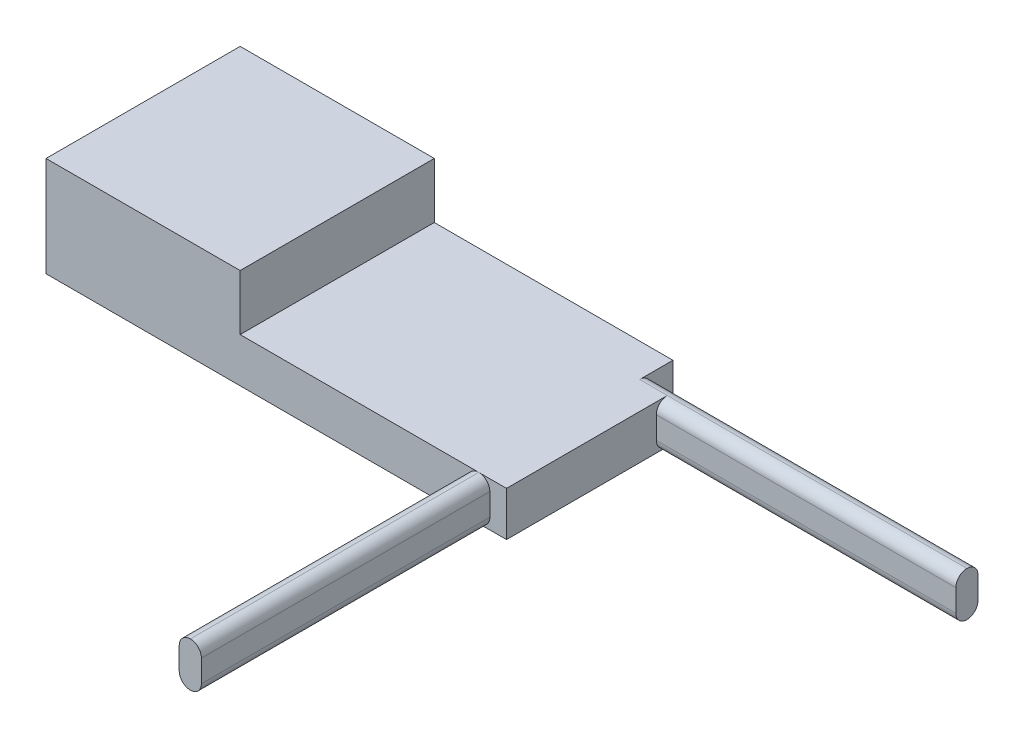
SolidWorks part; units mm, degrees
ref_plane "Front Plane" through (0, 0, 0) normal (0, 0, 1) x (1, 0, 0)
ref_plane "Top Plane" through (0, 0, 0) normal (0, 1, 0) x (1, 0, 0)
ref_plane "Right Plane" through (0, 0, 0) normal (1, 0, 0) x (0, 0, -1)
sketch "Sketch2" plane through (0, 0, 0) normal (0, 1, 0) x (1, 0, 0)
  line L0 (0, 0) -> (26.5, 0)
  line L4 (29, 15.5) -> (27.5, 15.5)
  line L5 (27.5, 15.5) -> (27.5, 17.5)
  line L6 (27.5, 17.5) -> (2.991, 17.5)
  line L8 (29, 15.5) -> (57, 15.5)
  line L9 (30, 13.5) -> (57, 13.5)
  line L10 (57, 13.5) -> (57, 15.5)
  line L11 (-11.509, 17.5) -> (2.991, 17.5)
  line L12 (28.5, 0) -> (28.5, -26)
  line L13 (26.5, -26) -> (28.5, -26)
  line L14 (26.5, -26) -> (26.5, 0)
  line L15 (28.5, 0) -> (30, 0)
  line L16 (30, 13.5) -> (30, 0)
  line L18 (-11.509, 17.5) -> (-11.509, 0)
  line L19 (-11.509, 0) -> (0, 0)
  dimension "D1" = 14.5
extrude "Boss-Extrude1" add sketch "Sketch2" along normal blind 4
fillet "Fillet1" radius 1 8 edges at (42.25, 0, -15.5) (28.5, 0, 13) (26.5, 0, 13) (43.5, 0, -13.5) (42.25, 4, -15.5) (43.5, 4, -13.5) (28.5, 4, 13) (26.5, 4, 13)
sketch "Sketch4" plane through (0, 4, 0) normal (0, 1, 0) x (1, 0, 0)
  line L0 (-11.509, 0) -> (27.5, 0) construction
  line L1 (-11.509, 17.5) -> (5.991, 17.5)
  line L2 (-11.509, 17.5) -> (-11.509, 0)
  line L3 (-11.509, 0) -> (5.991, 0)
  line L4 (5.991, 17.5) -> (5.991, 0)
  dimension "D1" = 17.5
extrude "Boss-Extrude3" add sketch "Sketch4" along normal blind 5
